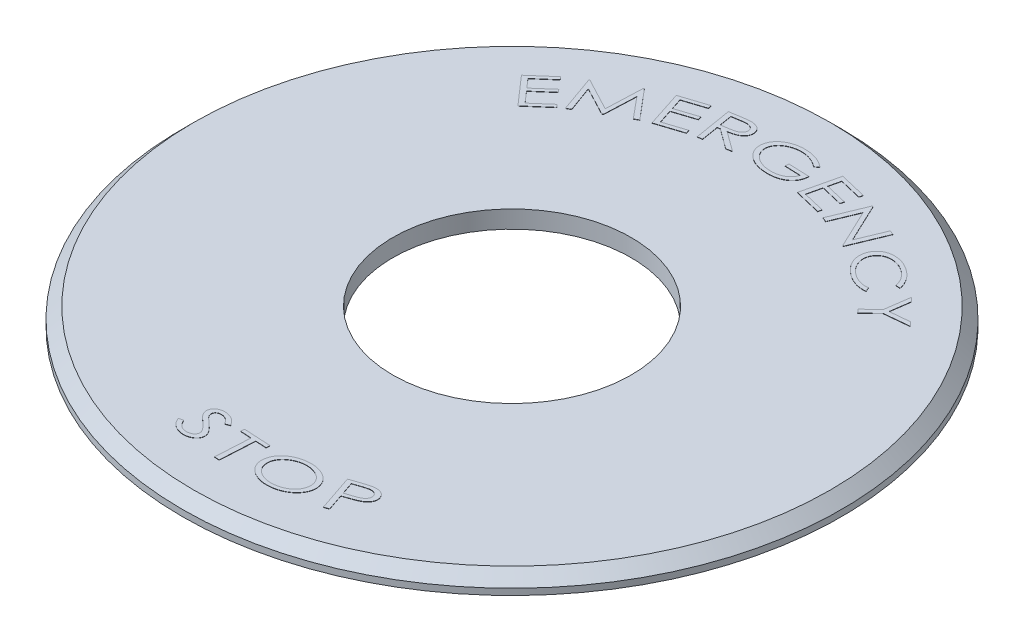
SolidWorks part; units mm, degrees
material "Plain Carbon Steel"
ref_plane "Front Plane" through (0, 0, 0) normal (0, 0, 1) x (1, 0, 0)
ref_plane "Top Plane" through (0, 0, 0) normal (0, 1, 0) x (1, 0, 0)
ref_plane "Right Plane" through (0, 0, 0) normal (1, 0, 0) x (0, 0, -1)
sketch "Sketch1" plane through (0, 0, 0) normal (0, 1, 0) x (1, 0, 0)
  circle A0 centre (0, 0) radius 29.845
  circle A1 centre (0, 0) radius 10.795
  dimension "D1" = 59.69
  dimension "D2" = 21.59
extrude "Extrude1" add sketch "Sketch1" along normal blind 1.5875
chamfer "Chamfer1" distance 1.016 angle 45 1 edges at (0, 1.5875, 29.845)
sketch "Sketch3" plane through (0, 0, 0) normal (0, -1, 0) x (1, 0, 0)
  line L0 (0, 29.845) -> (0, 29.083) construction
  line L1 (0, 29.083) -> (0, 13.97) construction
  line L2 (0, 13.97) -> (0, 0) construction
  line L3 (0, 0) -> (0, 10.033) construction
  line L4 (0, 10.033) -> (0, -13.97) construction
  line L5 (0, -13.97) -> (0, -29.083) construction
  line L6 (0, -29.083) -> (0, -29.845) construction
  line L7 (0.254, 29.0819) -> (0.254, 13.9677)
  line L8 (-0.254, 29.0819) -> (-0.254, 3.4654) construction
  line L9 (-0.254, 3.4654) -> (0, 3.4654) construction
  line L10 (0, 3.4654) -> (0.254, 3.4654) construction
  line L11 (20.4267, 20.702) -> (9.8454, 9.911)
  arc A0 (20.4267, 20.702) -> (-0.254, 29.0819) centre (0, 0) ccw
  arc A1 (9.8454, 9.911) -> (0.254, 13.9677) centre (0, 0) ccw
  circle A2 centre (0, 0) radius 10.795 construction
  circle A3 centre (0, 0) radius 29.845 construction
  dimension "D1" = 0.508
  dimension "D2" = 0.762
  dimension "D3" = 27.94
  dimension "D4" = 21.844
  dimension "D5" = 10.414
extrude "Extrude3" cut sketch "Sketch3" against normal blind 0.508 contours A1 L11 A0 L7 region at (8.4262, 0, 20.1838)
ref_axis "Axis1" through (0, 24.8873, 0) along (0, -1, 0)
pattern_circular "CirPattern1" count 8 over 360 about axis through (0, 24.8873, 0) along (0, -1, 0) of "Extrude3"
sketch "Sketch4" plane through (0, 0, 0) normal (0, -1, 0) x (1, 0, 0)
  circle A0 centre (0, 0) radius 11.557
  circle A1 centre (0, 0) radius 13.208
  arc A2 (-0.0464, 13.9699) -> (-9.697, 10.0563) centre (0, 0) ccw construction
  circle A3 centre (0, 0) radius 10.795 construction
  dimension "D1" = 0.762
  dimension "D2" = 0.762
extrude "Extrude4" cut sketch "Sketch4" against normal blind 0.508
sketch "Sketch5" plane through (0, 1.5875, 0) normal (0, 1, 0) x (1, 0, 0)
  circle A0 centre (0, 0) radius 25.4 construction
  circle A1 centre (0, 0) radius 22.225 construction
  text T0 "EMERGENCY         " font "Century Gothic" height in points 13
  text T1 "                                              STOP" font "Century Gothic" height 3.5
  dimension "D1" = 50.8
  dimension "D2" = 44.45
extrude "Extrude5" add sketch "Sketch5" along normal blind 0.0254
